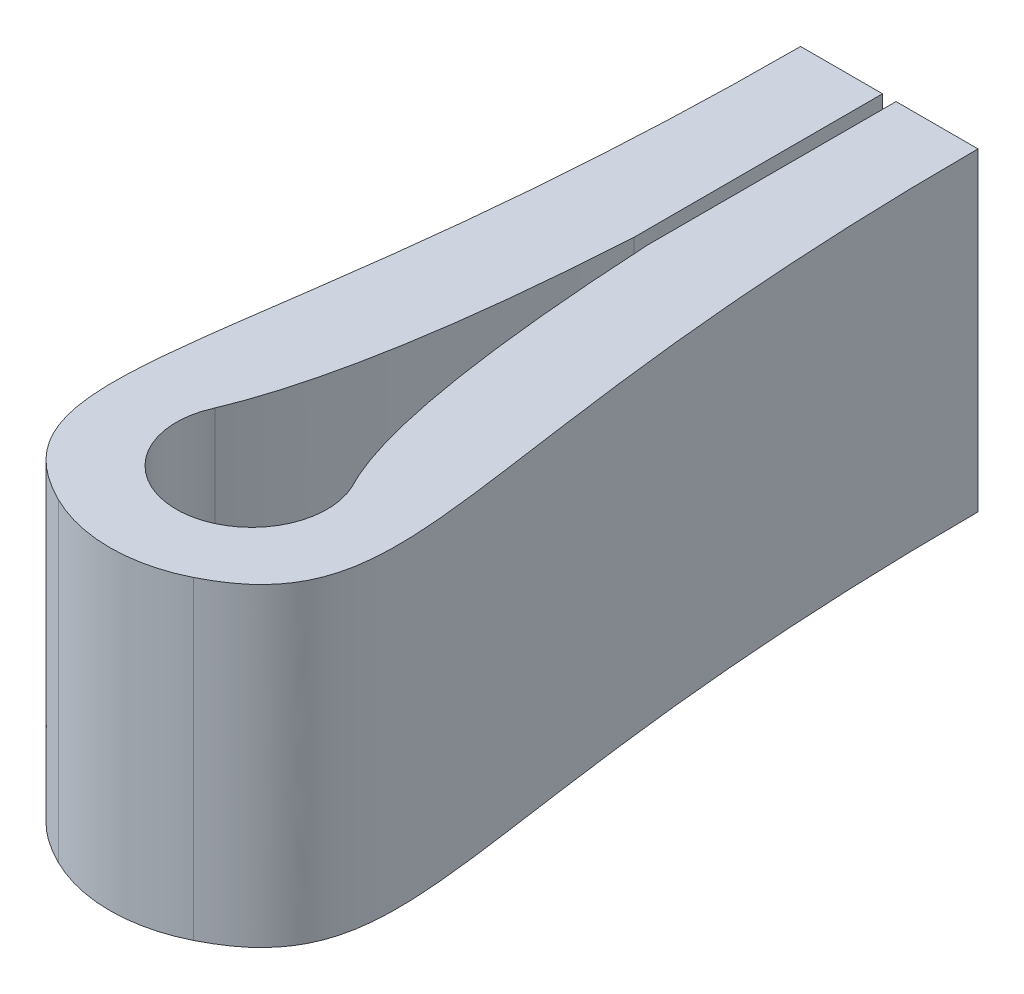
SolidWorks part; units mm, degrees
ref_plane "Front Plane" through (0, 0, 0) normal (0, 0, 1) x (1, 0, 0)
ref_plane "Top Plane" through (0, 0, 0) normal (0, 1, 0) x (1, 0, 0)
ref_plane "Right Plane" through (0, 0, 0) normal (1, 0, 0) x (0, 0, -1)
sketch "Sketch1" plane through (0, 0, 0) normal (0, 1, 0) x (1, 0, 0)
  line L0 (0, 0) -> (0, 6.2146) construction
  line L1 (-0.6908, 2.6065) -> (-0.2172, 3.7387) construction
  line L2 (-0.0683, 8.724) -> (0.0683, 8.724)
  line L3 (-0.0683, 8.724) -> (-0.0683, 6.2146)
  line L5 (0.0683, 8.724) -> (0.0683, 6.2146)
  line L6 (-0.2172, 3.7387) -> (-0.0683, 6.2146) construction
  line L9 (0.6908, 2.6065) -> (0.2181, 3.4821) construction
  line L10 (0.2181, 3.4821) -> (0.0683, 6.2146) construction
  line L11 (-0.8958, 8.724) -> (-0.8958, 4.5422) construction
  line L12 (-0.8958, 4.5422) -> (-1.5887, 2.2193) construction
  line L20 (-1.5887, 2.2193) -> (-2.0882, 1.3377) construction
  line L21 (-2.0882, 1.3377) -> (0, 0.7662) construction
  line L22 (0.8958, 8.724) -> (0.8958, 4.5422) construction
  line L23 (0.8958, 4.5422) -> (1.5887, 2.2193) construction
  line L25 (1.5887, 2.2193) -> (2.0882, 1.3377) construction
  line L26 (2.0882, 1.3377) -> (0, 0.7662) construction
  line L27 (-0.8958, 8.724) -> (0, 8.724)
  line L28 (0.8958, 8.724) -> (0, 8.724)
  arc A0 (-0.6908, 2.6065) -> (0.6908, 2.6065) centre (0, 2.2849) ccw
  spline S3 degree 2 poles (0.6908, 2.6065) (0.2181, 3.4821) (0.0683, 6.2146) knots 0 0 0 1 1 1
  spline S4 degree 2 poles (-0.6908, 2.6065) (-0.2172, 3.7387) (-0.0683, 6.2146) knots 0 0 0 1 1 1
  spline S5 degree 4 poles (-0.8958, 8.724) (-0.8958, 4.5422) (-1.5887, 2.2193) (-2.0882, 1.3377) (0, 0.7662) knots 0 0 0 0 0 1 1 1 1 1
  spline S6 degree 4 poles (0.8958, 8.724) (0.8958, 4.5422) (1.5887, 2.2193) (2.0882, 1.3377) (0, 0.7662) knots 0 0 0 0 0 1 1 1 1 1
  point P2 (0, 0)
  point P6 (0, 0)
  point P7 (0, 0)
  point P8 (-0.508, -2.5134)
  point P18 (0.508, -2.5134)
  point P21 (0, -2.54)
  dimension "D1" = 1.524
extrude "Boss-Extrude1" add sketch "Sketch1" along normal blind 1.5875 and the other way blind 1.5875 contours S6 L28 L5 S3 A0 S4 L3 L27 S5 region at (-0.1529, 0, -7.4693)
ref_axis "Axis1" through (0, 0, -2.032) along (0, 0, 1)
ref_plane "Plane1" through (0, 0, 2.54) normal (0, 0, 1) x (1, 0, 0)
ref_axis "Axis2" through (0, 1.7463, 2.54) along (0, -1, 0)
fillet "Fillet1" radius 1.524 1 edges at (0, 0, -0.7662)
ref_plane "Plane2" through (0, 0, -2.6065) normal (0, 0, -1) x (-1, 0, 0)
ref_plane "Plane3" through (0, 0, -3.1145) normal (0, 0, -1) x (-1, 0, 0)
